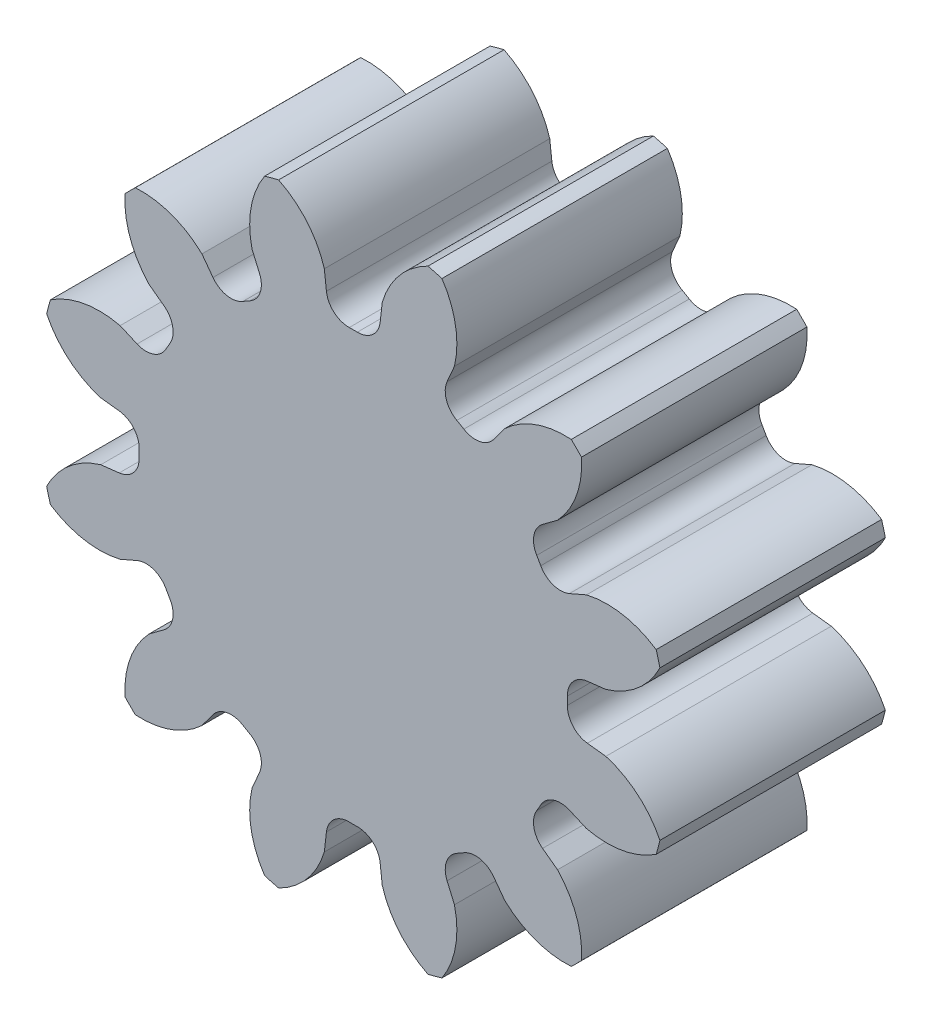
SolidWorks part; units mm, degrees
ref_plane "前视基准面" through (0, 0, 0) normal (0, 0, 1) x (1, 0, 0)
ref_plane "上视基准面" through (0, 0, 0) normal (0, 1, 0) x (1, 0, 0)
ref_plane "右视基准面" through (0, 0, 0) normal (1, 0, 0) x (0, 0, -1)
sketch "Sketch1" plane through (0, 0, 0) normal (0, 0, 1) x (1, 0, 0)
  line L0 (0, 0) -> (2.5197, 5.0438) construction
  line L1 (0, 0) -> (0, 7) construction
  line L2 (0, 0) -> (1.8117, 6.7615) construction
  line L3 (0, 0) -> (0.6426, 5.6014)
  line L4 (0, 0) -> (-0.6426, 5.6014)
  circle A0 centre (0, 0) radius 7
  circle A1 centre (0, 0) radius 4.75
  circle A2 centre (0, 0) radius 6 construction
  circle A3 centre (0, 0) radius 5.6382 construction
  arc A4 (0.6426, 5.6014) -> (1.6562, 6.8013) centre (2.5197, 5.0438) cw
  arc A5 (0.7832, 5.9487) -> (1.5529, 5.7956) centre (0, 0) cw
  arc A6 (-0.6426, 5.6014) -> (-1.6562, 6.8013) centre (-2.5197, 5.0438) ccw
  point P11 (1.5529, 5.7956)
  point P12 (0.7832, 5.9487)
  dimension "da" = 14
  dimension "df" = 9.5
  dimension "db" = 11.2763
  dimension "dp" = 12
  dimension "deg_from180" = 15
  dimension "alpha" = 20
  dimension "s_half" = 0.7854
extrude "Da_circle" add sketch "Sketch1" along normal mid plane 5 contours A0
extrude "one_teeth" cut sketch "Sketch" against normal through all both and the other way through all contours A6 L4 A1 L3 A4 A0 region at (0, 6.0686, 0)
sketch "Sketch" plane through (0, 0, 0) normal (0, 0, 1) x (1, 0, 0) same geometry as "Sketch1"
fillet "Fillet_for_high" radius 0.5 2 edges at (-0.5414, 4.719, 0) (0.5414, 4.719, 0)
pattern_circular "CirPattern_for_high" count 12 over 360 about axis through (0, 0, 2.5) along (0, 0, -1) of "one_teeth", "Fillet_for_high" reverse direction yes
fillet "Fillet_for_low" [suppressed] radius 0.1
pattern_circular "CirPattern_for_low" [suppressed] count 12 over 360 of bodies 107
